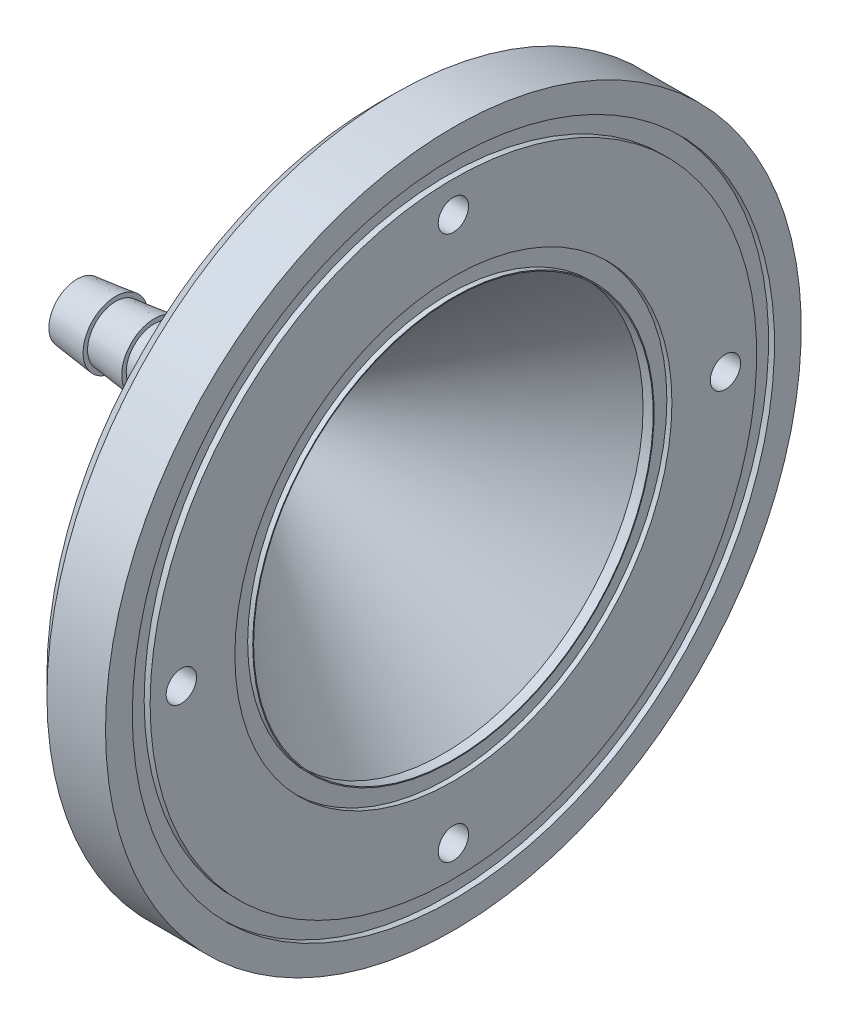
SolidWorks part; units mm, degrees
ref_plane "Front Plane" through (0, 0, 0) normal (0, 0, 1) x (1, 0, 0)
ref_plane "Top Plane" through (0, 0, 0) normal (0, 1, 0) x (1, 0, 0)
ref_plane "Right Plane" through (0, 0, 0) normal (1, 0, 0) x (0, 0, -1)
sketch "Sketch1" plane through (0, 0, 0) normal (0, 0, 1) x (1, 0, 0)
  line L0 (-801.9206, 0) -> (36107.5283, 0) construction
  line L3 (-14.1752, 3.65) -> (-14.1752, 3.15)
  line L8 (-18.5085, 1.9) -> (0, 1.9)
  line L9 (-18.5085, 1.9) -> (-18.5085, 3.15)
  line L10 (23.6874, 24.5) -> (23.6874, 39)
  line L12 (23.6874, 39) -> (15.1214, 39)
  line L16 (23.6874, 24.5) -> (23.1214, 24.5)
  line L17 (23.1214, 24.5) -> (23.1214, 22.4)
  line L18 (15.1214, 39) -> (15.1214, 22.4)
  line L20 (0, 1.9) -> (22.5554, 22.4)
  line L21 (-18.5085, 3.15) -> (-14.1752, 3.65)
  line L22 (22.5554, 22.4) -> (23.1214, 22.4)
  line L23 (-14.1752, 3.15) -> (-9.8419, 3.65)
  line L25 (-9.8419, 3.15) -> (-5.5085, 3.65)
  line L26 (-9.8419, 3.65) -> (-9.8419, 3.15)
  line L27 (-5.5085, 3.65) -> (15.1214, 22.4)
  line L29 (23.0204, 36) -> (23.0204, 34)
  line L30 (23.0204, 34) -> (23.6874, 34)
  line L32 (23.0204, 36) -> (23.6874, 36)
  line L33 (23.1214, 22.5) -> (23.6874, 22.5)
  line L34 (23.6874, 22.5) -> (23.6874, 22.4)
  line L35 (23.6874, 22.4) -> (23.1214, 22.4)
  dimension "D3" = 0.566
  dimension "D2" = 7.3
  dimension "D6" = 3.8
  dimension "D7" = 6.3
  dimension "D5" = 39
  dimension "D8" = 24.5
  dimension "D10" = 2.1
  dimension "D4" = 5
  dimension "D9" = 0.566
  dimension "D11" = 13
  dimension "D12" = 8.566
  dimension "D14" = 2
  dimension "D13" = 36
  dimension "D15" = 0.667
  dimension "D16" = 0.1
revolve "Revolve17" add sketch "Sketch1" angle 360 about L0 region at (-14.7371, 3.4, 0) region at (23.4044, 22.45, 0)
sketch "Sketch4" plane through (15.1214, 0, 0) normal (-1, 0, 0) x (0, 0, 1)
  line L0 (0, 22.4) -> (0, 39) construction
  circle A0 centre (0, 0) radius 30.5 construction
  circle A1 centre (0, 0) radius 22.4 construction
  circle A2 centre (0, 0) radius 39 construction
  point P3 (0, 30.5)
  point P7 (30.5, 0)
  point P12 (-30.5, 0)
  point P13 (0, -30.5)
  dimension "D1" = 8.5
  dimension "D2" = 8.5
hole_wizard "CBORE for M3 Hex Socket Head Cap Screw2" positions "Sketch4" profile "Sketch5" counterbore size "M3" standard "ISO"
sketch "Sketch5" plane through (15.1214, -30.5, 0) normal (0, 1, 0) x (0, 0, 1)
  line L0 (0, 0) -> (0, 9.5875)
  line L1 (0, 9.5875) -> (1.7, 8.566)
  line L2 (1.7, 8.566) -> (1.7, 3.4)
  line L3 (1.7, 3.4) -> (3.25, 3.4)
  line L4 (3.25, 3.4) -> (3.25, 0)
  line L5 (3.25, 0) -> (0, 0)
  line L10 (0, 9.5875) -> (-1.7, 8.566) construction
  line L11 (0, -6.35) -> (0, 107.95) construction
  dimension "Hole Dia." = 3.4
  dimension "Hole Depth" = 8.566
  dimension "C'Bore Dia." = 6.5
  dimension "C'Bore Depth" = 3.4
  dimension "Drill Angle" = 118
chamfer "Chamfer1" distance 2 angle 45 1 edges at (15.1214, 0, 39)
sketch "Sketch6" plane through (23.6874, 0, 0) normal (1, 0, 0) x (0, 0, -1)
  line L0 (0, 39) -> (0, 24.5)
  circle A0 centre (0, 0) radius 39
  circle A1 centre (0, 0) radius 39 construction
  circle A2 centre (0, 0) radius 24.5 construction
equation "\"D9@Sketch1\"=\"D3@Sketch1\""
